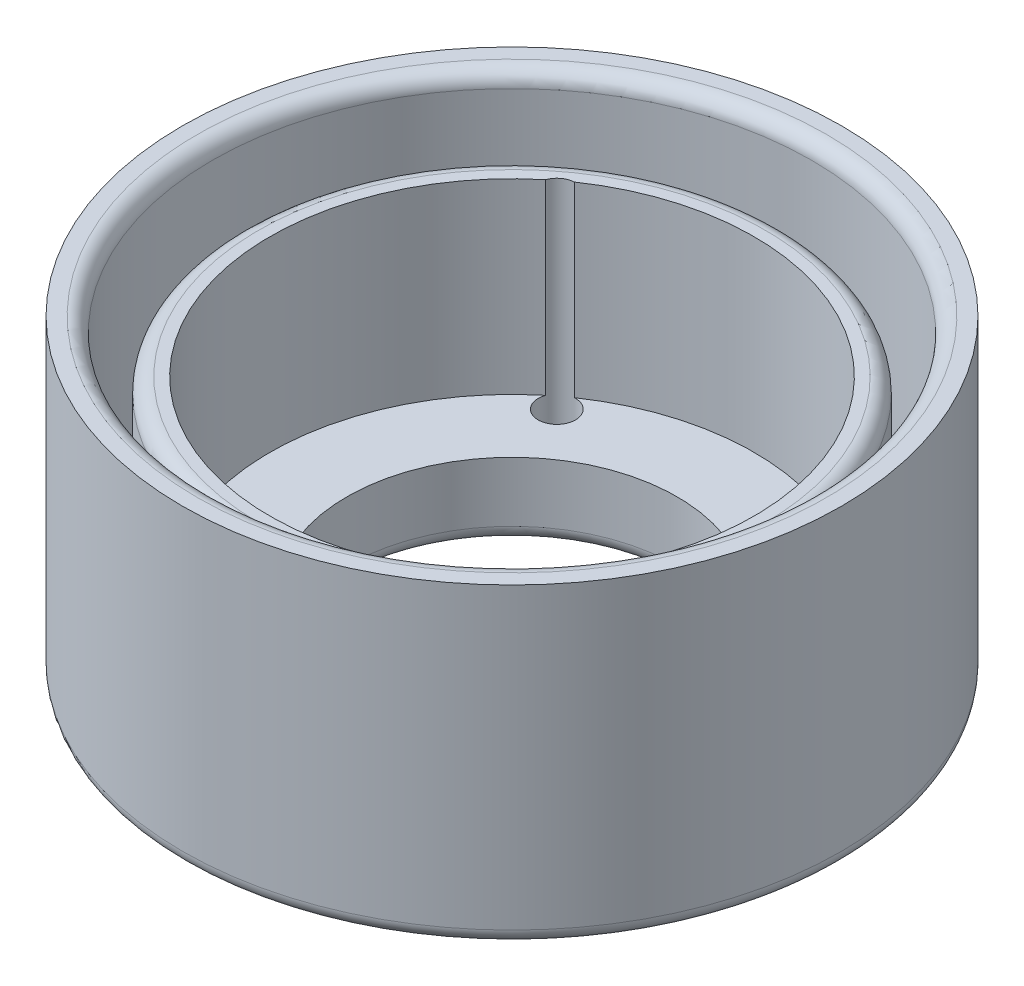
SolidWorks part; units mm, degrees
ref_plane "Alzado" through (0, 0, 0) normal (0, 0, 1) x (1, 0, 0)
ref_plane "Planta" through (0, 0, 0) normal (0, 1, 0) x (1, 0, 0)
ref_plane "Vista lateral" through (0, 0, 0) normal (1, 0, 0) x (0, 0, -1)
sketch "Croquis1" plane through (0, 0, 0) normal (0, 1, 0) x (1, 0, 0)
  circle A0 centre (0, 0) radius 17.95
  circle A1 centre (0, 0) radius 20.05
  circle A2 centre (0, 0) radius 22.05
  circle A3 centre (0, 0) radius 16.2
  dimension "D1" = 35.9
  dimension "D2" = 1.75
  dimension "D3" = 40.1
  dimension "D4" = 2
extrude "Saliente-Extruir1" add sketch "Croquis1" along normal blind 16 contours A2 A1 region at (-21.4263, 0, 0)
extrude "Saliente-Extruir2" add sketch "Croquis1<4>" along normal blind 12.5 separate body contours A0 A3 region at (-17.4423, 0, 0)
sketch "Croquis1<4>" plane through (0, 0, 0) normal (0, 1, 0) x (1, 0, 0) same geometry as "Croquis1"
extrude "Saliente-Extruir4" add sketch "Croquis1<6>" against normal blind 5 contours A3 | A0 A3 | A1 A0 | A2 A1 region at (-17.4423, 0, 0) region at (-19.4829, 0, 0) region at (-21.4263, 0, 0) region at (0, 0, 0)
sketch "Croquis1<6>" plane through (0, 0, 0) normal (0, 1, 0) x (1, 0, 0) same geometry as "Croquis1"
sketch "Croquis4" plane through (0, -5, 0) normal (0, -1, 0) x (1, 0, 0)
  line L0 (9.1, 12.1) -> (0, 0) construction
  line L1 (0, 0) -> (-9.1, -12.1) construction
  line L3 (13, 16) -> (-13, 16) construction
  line L4 (13, 16) -> (13, -16) construction
  line L5 (13, -16) -> (-13, -16) construction
  line L6 (-13, 16) -> (-13, -16) construction
  line L7 (13, 16) -> (-13, -16) construction
  line L8 (13, -16) -> (-13, 16) construction
  circle A0 centre (0, 0) radius 11.05
  circle A1 centre (9.1, 12.1) radius 1.25
  circle A2 centre (-9.1, -12.1) radius 1.25
  point P11 (9.1, 13.35)
  point P12 (10.35, 12.1)
  dimension "D1" = 22.1
  dimension "D4" = 2.5
  dimension "D2" = 26
  dimension "D3" = 32
  dimension "D5" = 2.65
  dimension "D6" = 2.65
extrude "Cortar-Extruir1" cut sketch "Croquis4" against normal up to next
sketch "Croquis5" plane through (0, -5, 0) normal (0, -1, 0) x (1, 0, 0)
  circle A0 centre (9.1, 12.1) radius 2.5
  circle A1 centre (-9.1, -12.1) radius 2.5
  circle A2 centre (9.1, 12.1) radius 1.25 construction
  circle A3 centre (-9.1, -12.1) radius 1.25 construction
  circle A4 centre (9.1, 12.1) radius 1.25
  circle A5 centre (-9.1, -12.1) radius 1.25
  dimension "D1" = 5
extrude "Cortar-Extruir2" cut sketch "Croquis5" against normal blind 3
fillet "Redondeo1" radius 1 1 edges at (0, -5, -11.05)
fillet "Redondeo3" radius 1 1 edges at (0, -5, 22.05)
fillet "Redondeo4" radius 1 2 edges at (0, 16, 20.05) (0, 12.5, 17.95)
